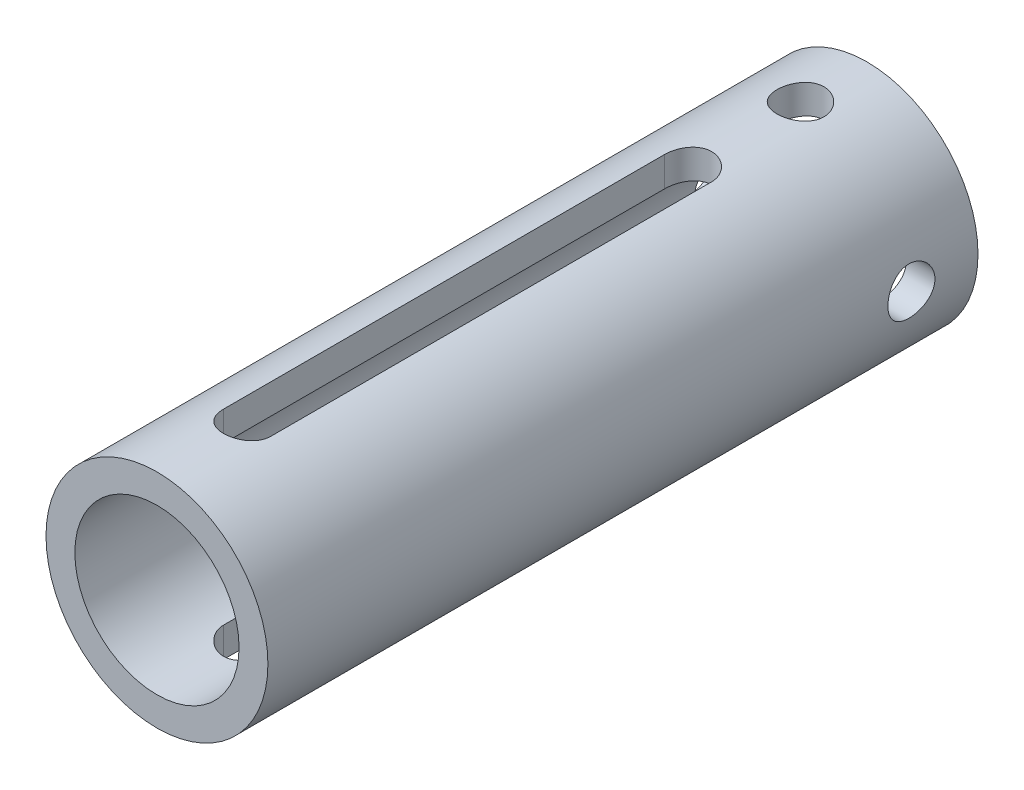
SolidWorks part; units mm, degrees
ref_plane "Front" through (0, 0, 0) normal (0, 0, 1) x (1, 0, 0)
ref_plane "Top" through (0, 0, 0) normal (0, 1, 0) x (1, 0, 0)
ref_plane "Right" through (0, 0, 0) normal (1, 0, 0) x (0, 0, -1)
sketch "Sketch1" plane through (0, 0, 0) normal (0, 0, 1) x (1, 0, 0)
  circle A0 centre (0, 0) radius 15.875
  circle A1 centre (0, 0) radius 11.7475
  dimension "D1" = 31.75
  dimension "D2" = 23.495
extrude "Boss-Extrude1" add sketch "Sketch1" along normal blind 101.6
hole_wizard "1/4 Clearance Slot1" positions "Sketch3" profile "Sketch2" size "1/4" standard "ANSI Inch" slot yes end condition through all
sketch "Sketch3" plane through (0, 0, 0) normal (0, 1, 0) x (1, 0, 0)
  line L0 (0, -92.075) -> (0, -22.225) construction
  line L1 (-15.875, -101.6) -> (15.875, -101.6) construction
  point P0 (0, -57.15)
  dimension "D1" = 9.525
sketch "Sketch2" plane through (0, 0, 57.15) normal (1, 0, 0) x (0, 0, -1)
  line L0 (0, 0) -> (0, 15.875)
  line L1 (0, 15.875) -> (3.3782, 15.875)
  line L2 (3.3782, 15.875) -> (3.3782, 0)
  line L5 (3.3782, 0) -> (0, 0)
  line L11 (0, -6.35) -> (0, 107.95) construction
  dimension "Thru Hole Dia." = 6.7564
  dimension "Thru Hole Depth" = 15.875
sketch "Sketch4" plane through (0, 0, 0) normal (0, 1, 0) x (1, 0, 0)
  line L0 (-3.3782, -88.6968) -> (-3.3782, -25.6032) construction
  line L1 (3.3782, -88.6968) -> (3.3782, -25.6032) construction
  line L2 (-3.3782, -88.6968) -> (-3.3782, -25.6032)
  line L3 (3.3782, -88.6968) -> (3.3782, -25.6032)
  arc A0 (3.3782, -25.6032) -> (-3.3782, -25.6032) centre (0, -25.6032) ccw construction
  arc A1 (-3.3782, -88.6968) -> (3.3782, -88.6968) centre (0, -88.6968) ccw construction
  arc A2 (3.3782, -25.6032) -> (-3.3782, -25.6032) centre (0, -25.6032) ccw
  arc A3 (-3.3782, -88.6968) -> (3.3782, -88.6968) centre (0, -88.6968) ccw
extrude "Cut-Extrude1" cut sketch "Sketch4" against normal up to next
sketch "Sketch5" plane through (0, 0, 0) normal (0, 1, 0) x (1, 0, 0)
  line L0 (0, 0) -> (0, -19.8802) construction
  line L1 (15.875, 0) -> (-15.875, 0) construction
  circle A0 centre (0, -9.525) radius 3.3655
  dimension "D1" = 6.731
  dimension "D2" = 9.525
extrude "Cut-Extrude2" cut sketch "Sketch5" against normal through all and the other way through all
sketch "Sketch6" plane through (0, 0, 0) normal (1, 0, 0) x (0, 0, -1)
  circle A0 centre (-9.525, 0) radius 3.3655
extrude "Cut-Extrude3" cut sketch "Sketch6" against normal through all and the other way through all
